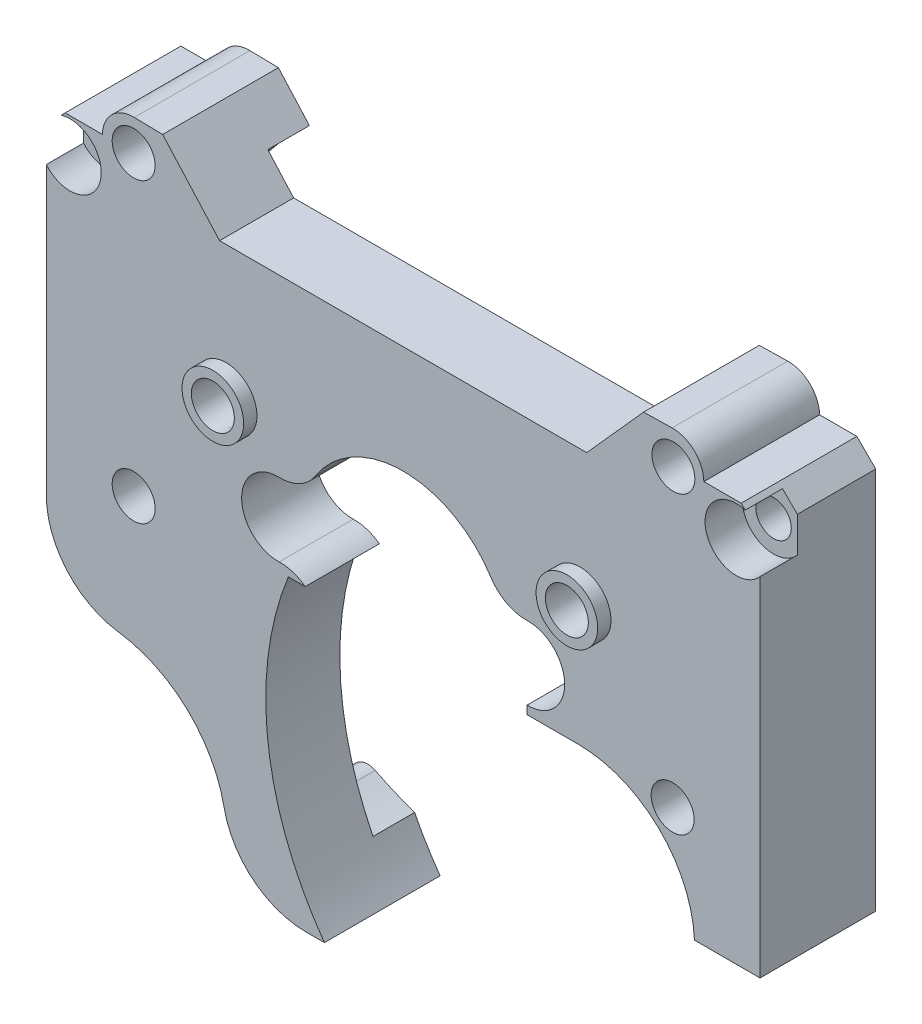
SolidWorks part; units mm, degrees
material "PET"
ref_plane "Front Plane" through (0, 0, 0) normal (0, 0, 1) x (1, 0, 0)
ref_plane "Top Plane" through (0, 0, 0) normal (0, 1, 0) x (1, 0, 0)
ref_plane "Right Plane" through (0, 0, 0) normal (1, 0, 0) x (0, 0, -1)
sketch "Sketch1" plane through (0, 0, 0) normal (0, 0, 1) x (1, 0, 0)
  circle A0 centre (0, 0) radius 24.7015
  circle A1 centre (0, 0) radius 7.9375
  dimension "D1" = 49.403
  dimension "D2" = 15.875
extrude "Boss-Extrude1" add sketch "Sketch1" along normal up to surface (5.65 mm away)
hole_wizard "CBORE SLOT for #2 Pan Head Machine Screw1" positions "Sketch13" profile "Sketch12" size "#2" standard "ANSI Inch" slot yes end condition through all
sketch "Sketch13" plane through (0, 0, 0) normal (0, 0, -1) x (-1, 0, 0)
  line L0 (-2.0066, 13.2132) -> (-2.0066, 19.5632) construction
  line L2 (7.493, 13.2132) -> (7.493, 19.5632) construction
  line L4 (-1.8669, 13.2132) -> (-2.1463, 13.2132) construction
  circle A1 centre (7.493, 14.3181) radius 1.1049 construction
  point P9 (-2.0066, 16.3882)
  point P11 (7.493, 16.3882)
  dimension "D1" = 6.35
sketch "Sketch12" plane through (2.0066, 16.3882, 0) normal (1, 0, 0) x (0, 1, 0)
  line L0 (0, 0) -> (0, 5.65)
  line L1 (0, 5.65) -> (1.3525, 5.65)
  line L3 (1.3525, 5.65) -> (1.3526, 1.5748)
  line L4 (2.3812, 1.5748) -> (1.3526, 1.5748)
  line L5 (2.3812, 1.5748) -> (2.3812, 1.0325)
  line L6 (2.3812, 1.0325) -> (3.4138, 0)
  line L7 (3.4138, 0) -> (0, 0)
  line L8 (-2.3812, 1.0325) -> (-3.4138, 0) construction
  line L11 (0, -6.35) -> (0, 107.95) construction
  dimension "Thru Hole Dia." = 2.7051
  dimension "Thru Hole Depth" = 5.65
  dimension "C'Bore Dia." = 4.7625
  dimension "C'Bore Depth" = 1.5748
  dimension "Near C'Sink Dia." = 6.8275
  dimension "Near C'Sink Angle" = 90
sketch "Sketch11" plane through (0, 0, 5.65) normal (0, 0, 1) x (1, 0, 0)
  line L0 (-24.2881, -4.5) -> (-11.876, -4.5)
  line L1 (-17.5, -4.5) -> (-13.5554, -4.5) construction
  line L2 (0, 0) -> (0, -12.7) construction
  line L3 (24.2881, -4.5) -> (11.876, -4.5)
  arc A0 (-11.876, -4.5) -> (11.876, -4.5) centre (0, 0) ccw
  arc A1 (-24.2881, -4.5) -> (24.2881, -4.5) centre (0, 0) ccw
  circle A2 centre (0, 0) radius 7.9375 construction
  dimension "D1" = 25.4
  dimension "D2" = 49.403
extrude "Boss-Extrude5" add sketch "Sketch11" along normal blind 12.7
sketch "Sketch17" plane through (0, 0, 5.65) normal (0, 0, 1) x (1, 0, 0)
  line L0 (-24.2881, -4.5) -> (-20.4781, -4.5)
  line L1 (-11.876, -4.5) -> (-24.2881, -4.5) construction
  line L2 (-20.4781, -4.5) -> (-20.4781, 4.39)
  line L3 (-13.4931, 20.6906) -> (-13.4931, 4.39) construction
  line L4 (-13.4931, 4.39) -> (-20.4781, 4.39) construction
  line L5 (0, 24.7015) -> (0, 0) construction
  line L6 (13.4931, 4.39) -> (20.4781, 4.39) construction
  line L7 (13.4931, 20.6906) -> (13.4931, 4.39) construction
  line L8 (20.4781, -4.5) -> (20.4781, 4.39)
  line L9 (24.2881, -4.5) -> (20.4781, -4.5)
  line L10 (-13.4931, 16.0175) -> (-13.4931, 20.6906)
  line L11 (13.4931, 16.0175) -> (13.4931, 20.6906)
  arc A0 (-13.4931, 20.6906) -> (-24.2881, -4.5) centre (0, 0) ccw
  arc A1 (24.2881, -4.5) -> (-24.2881, -4.5) centre (0, 0) ccw construction
  arc A2 (13.4931, 20.6906) -> (24.2881, -4.5) centre (0, 0) cw
  arc A3 (-13.4931, 16.0175) -> (-20.4781, 4.39) centre (0, 0) ccw
  arc A4 (20.4781, 4.39) -> (13.4931, 16.0175) centre (0, 0) ccw
  dimension "D1" = 3.81
  dimension "D2" = 6.985
  dimension "D3" = 8.89
extrude "Boss-Extrude7" add sketch "Sketch17" along normal up to surface (12.7 mm away) up to face at (0, -11.6004, 18.35)
sketch "Sketch32" plane through (0, 0, 0) normal (0, 0, -1) x (-1, 0, 0)
  line L0 (-18.3768, 26.4668) -> (18.3768, 26.4668) construction
  line L1 (-27.4725, 17.3712) -> (-18.3768, 26.4668) construction
  line L2 (-27.4725, -17.6276) -> (-27.4725, 17.3712) construction
  line L3 (18.3768, -26.4668) -> (-18.6333, -26.4668) construction
  line L4 (27.4725, -17.3712) -> (18.3768, -26.4668) construction
  line L5 (27.4725, 17.3712) -> (27.4725, -17.3712) construction
  line L6 (18.3768, 26.4668) -> (27.4725, 17.3712) construction
  line L7 (-18.3768, 26.4668) -> (18.3768, 26.4668) construction
  line L8 (-27.4725, 17.3712) -> (-18.3768, 26.4668) construction
  line L9 (-27.4725, -17.6276) -> (-27.4725, 17.3712) construction
  line L10 (18.3768, -26.4668) -> (-18.6333, -26.4668) construction
  line L11 (27.4725, -17.3712) -> (18.3768, -26.4668) construction
  line L12 (27.4725, 17.3712) -> (27.4725, -17.3712) construction
  line L13 (18.3768, 26.4668) -> (27.4725, 17.3712) construction
  line L14 (18.2716, 26.2128) -> (27.2185, 17.266)
  line L15 (27.2185, 17.266) -> (27.2185, -16.7395)
  line L16 (27.2185, -16.7395) -> (29.6895, -16.7395)
  line L17 (16.2895, -26.2128) -> (-18.2716, -26.2128)
  line L18 (-27.2185, -17.266) -> (-27.2185, 17.266)
  line L19 (-27.2185, 17.266) -> (-18.2716, 26.2128)
  line L20 (-18.2716, 26.2128) -> (18.2716, 26.2128)
  line L21 (27.2185, -17.266) -> (18.2716, -26.2128) construction
  line L23 (29.6895, -16.7395) -> (29.6895, -29.2395)
  line L24 (29.6895, -29.2395) -> (16.2895, -29.2395)
  line L25 (16.2895, -29.2395) -> (16.2895, -26.2128)
  line L26 (18.2716, -26.2128) -> (-18.6333, -26.2128) construction
  line L27 (27.2185, 17.266) -> (27.2185, -17.266) construction
  line L28 (-18.2716, -26.2128) -> (-27.2185, -17.266)
  line L29 (-27.2185, -17.6276) -> (-27.2185, 17.266) construction
  arc A0 (-27.4725, -17.6276) -> (-18.6333, -26.4668) centre (-18.6333, -17.6276) ccw construction
  circle A1 centre (0, 0) radius 24.7015
  circle A2 centre (0, 0) radius 24.7015
  arc A3 (-27.4725, -17.6276) -> (-18.6333, -26.4668) centre (-18.6333, -17.6276) ccw construction
  arc A5 (-27.2185, -17.6276) -> (-18.6333, -26.2128) centre (-18.6333, -17.6276) ccw construction
  dimension "D1" = 0
  dimension "D2" = 0.254
extrude "Boss-Extrude8" add sketch "Sketch32" against normal up to surface (18.35 mm away) up to face at (0, 1.1766, 18.35)
sketch "Sketch33" plane through (0, 0, 18.35) normal (0, 0, 1) x (1, 0, 0)
  line L1 (-13.4931, 20.6906) -> (13.4931, 20.6906)
  line L2 (-13.4931, 20.6906) -> (-13.4931, 22.4028)
  line L3 (-13.4931, 26.2128) -> (13.4931, 26.2128)
  line L4 (13.4931, 20.6906) -> (13.4931, 22.4028)
  line L5 (13.4931, 20.6906) -> (13.4931, 16.0175) construction
  line L6 (-18.2716, 26.2128) -> (18.2716, 26.2128) construction
  line L29 (-13.4931, 22.4028) -> (-13.4931, 26.2128)
  line L30 (13.4931, 26.2128) -> (13.4931, 22.4028)
extrude "Cut-Extrude1" cut sketch "Sketch33" against normal up to surface (12.7 mm away) up to face at (-7.9375, 0, 5.65)
sketch "Sketch35" plane through (0, 0, 18.35) normal (0, 0, 1) x (1, 0, 0)
  line L0 (20.4781, 4.39) -> (20.4781, -4.5) construction
  line L1 (13.4931, 26.2128) -> (13.4931, 16.0175) construction
  line L2 (-13.4931, 16.0175) -> (-13.4931, 26.2128) construction
  line L3 (-20.4781, -4.5) -> (-20.4781, 4.39) construction
  line L12 (-20.4781, -4.5) -> (-20.4781, 4.39)
  line L13 (-13.4931, 16.0175) -> (-13.4931, 25.6031)
  line L14 (13.4931, 25.6031) -> (13.4931, 16.0175)
  line L15 (20.4781, 4.39) -> (20.4781, -4.5)
  line L16 (-27.2185, -16.7395) -> (-27.2185, 17.266) construction
  line L17 (-27.2185, 17.266) -> (-18.2716, 26.2128) construction
  line L20 (18.2716, 26.2128) -> (27.2185, 17.266) construction
  line L21 (27.2185, 17.266) -> (27.2185, -17.266) construction
  line L22 (-27.2185, -16.7395) -> (-27.2185, 17.266) construction
  line L23 (-27.2185, 17.266) -> (-18.2716, 26.2128) construction
  line L24 (-23.4085, 15.6878) -> (-15.5775, 23.5187) construction
  line L25 (15.5775, 23.5187) -> (23.4085, 15.6878) construction
  line L26 (18.2716, 26.2128) -> (27.2185, 17.266) construction
  line L27 (27.2185, 17.266) -> (27.2185, -17.266) construction
  line L28 (-23.4085, -4.5) -> (-23.4085, 15.6878)
  line L29 (-23.4085, 15.6878) -> (-13.4931, 25.6031)
  line L30 (13.4931, 25.6031) -> (23.4085, 15.6878)
  line L31 (23.4085, 15.6878) -> (23.4085, -4.5)
  line L32 (-20.4781, -4.5) -> (-23.4085, -4.5)
  line L33 (20.4781, -4.5) -> (23.4085, -4.5)
  line L34 (-23.4085, -16.7395) -> (-23.4085, 15.6878) construction
  line L35 (23.4085, 15.6878) -> (23.4085, -17.266) construction
  arc A0 (20.4781, 4.39) -> (13.4931, 16.0175) centre (0, 0) ccw construction
  arc A1 (-13.4931, 16.0175) -> (-20.4781, 4.39) centre (0, 0) ccw construction
  arc A6 (-13.4931, 16.0175) -> (-20.4781, 4.39) centre (0, 0) ccw
  arc A7 (20.4781, 4.39) -> (13.4931, 16.0175) centre (0, 0) ccw
  dimension "D1" = 3.81
extrude "Cut-Extrude2" cut sketch "Sketch35" against normal up to surface (12.7 mm away) up to face at (-7.9375, 0, 5.65)
sketch "Sketch37" plane through (0, 0, 18.35) normal (0, 0, 1) x (1, 0, 0)
  line L16 (-23.4085, 15.6878) -> (-13.4931, 25.6031)
  line L17 (-13.4931, 25.6031) -> (-13.4931, 26.2128)
  line L18 (-13.4931, 26.2128) -> (-18.2716, 26.2128)
  line L19 (-18.2716, 26.2128) -> (-27.2185, 17.266)
  line L20 (-27.2185, 17.266) -> (-27.2185, -16.7395)
  line L21 (-27.2185, -16.7395) -> (-29.6895, -16.7395)
  line L22 (-16.2895, -26.2128) -> (18.2716, -26.2128)
  line L23 (27.2185, -17.266) -> (27.2185, 17.266)
  line L24 (27.2185, 17.266) -> (18.2716, 26.2128)
  line L25 (18.2716, 26.2128) -> (13.4931, 26.2128)
  line L26 (13.4931, 26.2128) -> (13.4931, 25.6031)
  line L27 (13.4931, 25.6031) -> (23.4085, 15.6878)
  line L28 (23.4085, 15.6878) -> (23.4085, -4.5)
  line L29 (23.4085, -4.5) -> (11.876, -4.5)
  line L30 (-11.876, -4.5) -> (-23.4085, -4.5)
  line L31 (-23.4085, -4.5) -> (-23.4085, 15.6878)
  line L32 (-23.4085, 15.6878) -> (-13.4931, 25.6031)
  line L33 (-13.4931, 25.6031) -> (-13.4931, 26.2128)
  line L34 (-13.4931, 26.2128) -> (-18.2716, 26.2128)
  line L35 (-18.2716, 26.2128) -> (-27.2185, 17.266)
  line L36 (-27.2185, 17.266) -> (-27.2185, -16.7395)
  line L37 (-27.2185, -16.7395) -> (-29.6895, -16.7395)
  line L38 (-16.2895, -26.2128) -> (18.2716, -26.2128)
  line L39 (27.2185, -17.266) -> (27.2185, 17.266)
  line L40 (27.2185, 17.266) -> (18.2716, 26.2128)
  line L41 (18.2716, 26.2128) -> (13.4931, 26.2128)
  line L42 (13.4931, 26.2128) -> (13.4931, 25.6031)
  line L43 (13.4931, 25.6031) -> (23.4085, 15.6878)
  line L44 (23.4085, 15.6878) -> (23.4085, -4.5)
  line L45 (23.4085, -4.5) -> (11.876, -4.5)
  line L46 (-11.876, -4.5) -> (-23.4085, -4.5)
  line L47 (-23.4085, -4.5) -> (-23.4085, 15.6878)
  line L52 (-29.6895, -16.7395) -> (-29.6895, -29.2395)
  line L53 (-29.6895, -16.7395) -> (-29.6895, -29.2395)
  line L54 (-29.6895, -29.2395) -> (-16.2895, -29.2395)
  line L55 (-29.6895, -29.2395) -> (-16.2895, -29.2395)
  line L56 (-16.2895, -29.2395) -> (-16.2895, -26.2128)
  line L57 (-16.2895, -29.2395) -> (-16.2895, -26.2128)
  line L58 (18.2716, -26.2128) -> (27.2185, -17.266)
  line L59 (18.2716, -26.2128) -> (27.2185, -17.266)
  arc A3 (-11.876, -4.5) -> (11.876, -4.5) centre (0, 0) ccw
  arc A5 (-11.876, -4.5) -> (11.876, -4.5) centre (0, 0) ccw
  dimension "D1" = 0
extrude "Cut-Extrude3" cut sketch "Sketch37" against normal up to surface (12.7 mm away) up to face at (-3.5089, 1.6246, 18.35)
hole_wizard "Hole1" positions "Sketch41" profile "Sketch40" legacy
sketch "Sketch41" plane through (0, 0, 5.65) normal (0, 0, 1) x (1, 0, 0)
  line L0 (-13.8885, -4) -> (-27.2185, -4) construction
  line L1 (-27.2185, 17.266) -> (-27.2185, -16.7395) construction
  line L3 (-20.5535, -4) -> (-20.5535, 26.2128) construction
  line L5 (18.2716, 26.2128) -> (-18.2716, 26.2128) construction
  line L6 (-20.5535, 26.2128) -> (-20.5535, 11.1064)
  line L10 (13.8885, -4) -> (27.2185, -4) construction
  line L11 (27.2185, -17.266) -> (27.2185, 17.266) construction
  point P0 (-20.5535, 18.6596)
  point P3 (-20.5535, -4)
  point P6 (20.6092, 18.5346)
  point P57 (20.5535, -4)
  point P58 (-20.5535, -4)
  point P60 (20.5535, -4)
  point P62 (-20.5535, 18.5346)
sketch "Sketch40" plane through (-20.5535, 18.6596, 5.65) normal (1, 0, 0) x (0, -1, 0)
  line L0 (0, 0) -> (0, 2.921)
  line L1 (0, 2.921) -> (1.4986, 2.921)
  line L2 (1.4986, 2.921) -> (1.6383, 0)
  line L3 (1.6383, 0) -> (0, 0)
  line L4 (0, 110) -> (0, -10) construction
  dimension "Minor Diameter" = 2.9972
  dimension "Depth" = 2.921
  dimension "Major Diameter" = 3.2766
hole_wizard "Ø3.0 (3) Diameter Hole1" positions "Sketch43" profile "Sketch42" hole size "Ø3.0" standard "ANSI Metric" end condition through all
sketch "Sketch43" plane through (0, 0, 5.65) normal (0, 0, 1) x (1, 0, 0)
  circle A0 centre (20.5535, -4) radius 1.4986 construction
  point P0 (-20.5535, 18.6596)
  point P3 (20.6092, 18.5346)
  point P6 (-20.5535, -4)
  point P13 (20.5535, -4)
  point P16 (0, 0)
  point P17 (0, 0)
  point P18 (0, 0)
sketch "Sketch42" plane through (-20.5535, 18.6596, 5.65) normal (1, 0, 0) x (0, -1, 0)
  line L0 (0, 0) -> (0, 5.65)
  line L1 (0, 5.65) -> (1.5, 5.65)
  line L2 (1.5, 5.65) -> (1.5, 0)
  line L5 (1.5, 0) -> (0, 0)
  line L11 (0, -6.35) -> (0, 107.95) construction
  dimension "Thru Hole Dia." = 3
  dimension "Thru Hole Depth" = 5.65
sketch "Sketch44" plane through (0, 0, 5.65) normal (0, 0, 1) x (1, 0, 0)
  line L0 (0, 0) -> (0, -7.9375) construction
  circle A0 centre (-9.525, 0) radius 2.794
  circle A1 centre (0, 0) radius 7.9375 construction
  circle A2 centre (9.525, 0) radius 2.794
  dimension "D1" = 5.588
extrude "Cut-Extrude4" cut sketch "Sketch44" against normal through all
fillet "Fillet1" radius 1.27 2 edges at (-16.2895, -26.2128, 2.825) (-27.2185, -16.7395, 2.825)
sketch "Sketch45" plane through (0, 0, 0) normal (0, 0, -1) x (-1, 0, 0)
  line L0 (22.9895, -29.2395) -> (22.9895, -22.9895) construction
  line L1 (16.2895, -29.2395) -> (29.6895, -29.2395) construction
  line L2 (22.9895, -22.9895) -> (29.6895, -22.9895) construction
  line L3 (29.6895, -29.2395) -> (29.6895, -16.7395) construction
  line L5 (19.5254, -16.9895) -> (16.0613, -22.9895)
  line L6 (16.0613, -22.9895) -> (19.5254, -28.9895)
  line L7 (19.5254, -28.9895) -> (26.4536, -28.9895)
  line L8 (26.4536, -28.9895) -> (29.9177, -22.9895)
  line L9 (29.9177, -22.9895) -> (26.4536, -16.9895)
  line L10 (26.4536, -16.9895) -> (19.5254, -16.9895)
  circle A0 centre (22.9895, -22.9895) radius 6 construction
  dimension "D1" = 12
extrude "Cut-Extrude5" cut sketch "Sketch45" against normal through all
sketch "Sketch46" plane through (0, 0, 0) normal (0, 0, -1) x (-1, 0, 0)
  line L14 (19.5254, -16.9895) -> (26.4536, -16.9895)
  line L15 (19.5254, -16.9895) -> (26.4536, -16.9895)
  line L16 (29.6895, -22.5942) -> (29.6895, -16.7395)
  line L17 (27.2185, -15.4695) -> (27.2185, 17.266)
  line L18 (27.2185, 17.266) -> (18.2716, 26.2128)
  line L19 (18.2716, 26.2128) -> (-18.2716, 26.2128)
  line L20 (-18.2716, 26.2128) -> (-27.2185, 17.266)
  line L21 (-27.2185, 17.266) -> (-27.2185, -17.266)
  line L22 (-27.2185, -17.266) -> (-18.2716, -26.2128)
  line L23 (-18.2716, -26.2128) -> (15.0195, -26.2128)
  line L24 (16.2895, -27.4828) -> (16.2895, -29.2395)
  line L25 (16.2895, -29.2395) -> (29.6895, -29.2395)
  line L26 (26.4536, -16.9895) -> (29.6895, -22.5942)
  line L27 (26.4536, -16.9895) -> (29.6895, -22.5942)
  line L28 (19.5254, -28.9895) -> (16.0613, -22.9895)
  line L29 (19.5254, -28.9895) -> (16.0613, -22.9895)
  line L30 (29.6895, -22.5942) -> (29.6895, -16.7395)
  line L31 (27.2185, -15.4695) -> (27.2185, 17.266)
  line L32 (27.2185, 17.266) -> (18.2716, 26.2128)
  line L33 (18.2716, 26.2128) -> (-18.2716, 26.2128)
  line L34 (-18.2716, 26.2128) -> (-27.2185, 17.266)
  line L35 (-27.2185, 17.266) -> (-27.2185, -17.266)
  line L36 (-27.2185, -17.266) -> (-18.2716, -26.2128)
  line L37 (-18.2716, -26.2128) -> (15.0195, -26.2128)
  line L38 (16.2895, -27.4828) -> (16.2895, -29.2395)
  line L39 (16.2895, -29.2395) -> (29.6895, -29.2395)
  line L40 (16.0613, -22.9895) -> (19.5254, -16.9895)
  line L41 (16.0613, -22.9895) -> (19.5254, -16.9895)
  line L46 (29.6895, -16.7395) -> (28.4885, -16.7395)
  line L47 (29.6895, -16.7395) -> (28.4885, -16.7395)
  line L48 (29.6895, -29.2395) -> (29.6895, -23.3847)
  line L49 (29.6895, -29.2395) -> (29.6895, -23.3847)
  line L50 (29.6895, -23.3847) -> (26.4536, -28.9895)
  line L51 (29.6895, -23.3847) -> (26.4536, -28.9895)
  line L52 (26.4536, -28.9895) -> (19.5254, -28.9895)
  line L53 (26.4536, -28.9895) -> (19.5254, -28.9895)
  circle A0 centre (0, 0) radius 23.8252 construction
  circle A1 centre (0, 0) radius 24.3332
  arc A7 (27.2185, -15.4695) -> (28.4885, -16.7395) centre (28.4885, -15.4695) ccw
  arc A8 (16.2895, -27.4828) -> (15.0195, -26.2128) centre (15.0195, -27.4828) ccw
  arc A11 (27.2185, -15.4695) -> (28.4885, -16.7395) centre (28.4885, -15.4695) ccw
  arc A12 (16.2895, -27.4828) -> (15.0195, -26.2128) centre (15.0195, -27.4828) ccw
  dimension "D1" = 47.6504
  dimension "D2" = 0.508
  dimension "D3" = 0
extrude "Boss-Extrude9" add sketch "Sketch46" along normal blind 3.175
fillet "Fillet3" radius 3.175 4 edges at (7.66, 2.0804, 2.825) (7.66, -2.0804, 2.825) (-7.66, -2.0804, 2.825) (-7.66, 2.0804, 2.825)
sketch "Sketch47" plane through (0, 0, 5.65) normal (0, 0, 1) x (1, 0, 0)
  line L0 (-29.6895, -22.5942) -> (-29.6895, -28.9895)
  line L1 (-29.6895, -28.9895) -> (-19.5254, -28.9895)
  line L2 (-29.6895, -22.5942) -> (-26.4536, -16.9895) construction
  line L3 (-26.4536, -16.9895) -> (-19.5254, -16.9895) construction
  line L4 (-19.5254, -16.9895) -> (-16.0613, -22.9895) construction
  line L5 (-16.0613, -22.9895) -> (-19.5254, -28.9895) construction
  line L6 (-29.6895, -22.5942) -> (-26.4536, -16.9895)
  line L7 (-26.4536, -16.9895) -> (-19.5254, -16.9895)
  line L8 (-19.5254, -16.9895) -> (-16.0613, -22.9895)
  line L9 (-16.0613, -22.9895) -> (-19.5254, -28.9895)
extrude "Boss-Extrude10" add sketch "Sketch47" against normal through all
fillet "Fillet2" radius 1.27 3 edges at (-29.6895, -16.7395, 1.2375) (-16.2895, -29.2395, 1.2375) (-29.6895, -29.2395, 1.2375)
sketch "Sketch48" plane through (0, 0, -3.175) normal (0, 0, -1) x (-1, 0, 0)
  circle A0 centre (22.9895, -22.9895) radius 9.525
  dimension "D1" = 19.05
extrude "Cut-Extrude6" cut sketch "Sketch48" against normal through all
fillet "Fillet4" radius 6.35 2 edges at (-14.0264, -26.2128, 1.2375) (-27.2185, -14.4548, 1.2375)
fillet "Fillet5" radius 1.27 2 edges at (-13.9718, -19.9222, -1.5875) (-19.9222, -13.9718, -1.5875)
hole_wizard "CBORE for #2 Pan Head Machine Screw1" positions "Sketch50" profile "Sketch49" counterbore size "#2" standard "ANSI Inch" end condition through all
sketch "Sketch50" plane through (0, 0, 5.65) normal (0, 0, 1) x (1, 0, 0)
  point P0 (-25.4059, 16.1162)
  point P3 (25.4059, 16.1162)
  point P6 (17.2045, -24.6819)
sketch "Sketch49" plane through (-25.4059, 16.1162, 5.65) normal (1, 0, 0) x (0, -1, 0)
  line L0 (0, 0) -> (0, 8.825)
  line L1 (0, 8.825) -> (1.3525, 8.825)
  line L3 (1.3525, 8.825) -> (1.3525, 2.8448)
  line L4 (1.3525, 2.8448) -> (2.3812, 2.8448)
  line L5 (2.3812, 2.8448) -> (2.3812, 0)
  line L7 (2.3812, 0) -> (0, 0)
  line L11 (0, -6.35) -> (0, 107.95) construction
  dimension "Thru Hole Dia." = 2.7051
  dimension "Thru Hole Depth" = 8.825
  dimension "C'Bore Dia." = 4.7625
  dimension "C'Bore Depth" = 2.8448
sketch "Sketch51" plane through (0, 0, -3.175) normal (0, 0, 1) x (1, 0, 0)
  line L0 (-8.7558, -3.429) -> (13.335, -3.429)
  line L1 (7.0488, -18.6052) -> (-3.503, -29.157)
  line L2 (13.335, -12.319) -> (7.0488, -18.6052) construction
  arc A0 (-8.7558, -3.429) -> (-3.503, -29.157) centre (13.335, -12.319) ccw
  arc A1 (7.0488, -18.6052) -> (13.335, -3.429) centre (13.335, -12.319) ccw
  point P1 (0, 0)
  dimension "D1" = 47.625
  dimension "D2" = 17.78
  dimension "D3" = 45
extrude "Cut-Extrude7" cut sketch "Sketch51" along normal up to next
sketch "Sketch52" plane through (0, 0, 5.65) normal (0, 0, 1) x (1, 0, 0)
  line L0 (27.2185, -17.266) -> (27.2185, 14.5718) construction
  line L1 (9.4546, -2.7931) -> (5.9351, -2.7931)
  line L2 (9.4546, -2.7931) -> (9.4546, -5.2705)
  line L3 (9.4546, -5.2705) -> (5.9351, -5.2705)
  line L4 (5.9351, -2.7931) -> (5.9351, -5.2705)
  line L5 (-5.9351, -5.2705) -> (-6.6961, -5.2705)
  line L6 (-5.9351, -5.2705) -> (-5.9351, -4.2622)
  line L7 (-5.9351, -4.2622) -> (-6.6961, -4.2622)
  line L8 (-6.6961, -5.2705) -> (-6.6961, -4.2622)
  line L9 (27.2185, -11.9378) -> (-0.5588, -11.9378)
  line L10 (27.2185, -11.9378) -> (27.2185, -26.2128)
  line L11 (27.2185, -26.2128) -> (-0.5588, -26.2128)
  line L12 (-0.5588, -11.9378) -> (-0.5588, -26.2128)
  line L13 (7.0488, -18.6052) -> (7.0488, -5.2705) construction
  point P22 (7.0488, -11.9378)
extrude "Cut-Extrude8" cut sketch "Sketch52" against normal through all body kept at (18.2716, 26.2128, 5.65)
sketch "Sketch53" plane through (0, 0, 5.65) normal (0, 0, 1) x (1, 0, 0)
  circle A4 centre (13.5, 6) radius 2.35 construction
  circle A5 centre (13.5, 6) radius 2.35
  circle A6 centre (-13.5, 6) radius 2.35 construction
  circle A7 centre (-13.5, 6) radius 2.35
extrude "Boss-Extrude11" add sketch "Sketch53" along normal up to surface (1.013 mm away)
fillet "Fillet6" [suppressed] radius 2.54
sketch "Sketch54" plane through (0, 0, 0) normal (0, 0, -1) x (-1, 0, 0)
  line L2 (1.4072, 14.5658) -> (1.4072, 18.2107)
  line L3 (-5.4204, 18.2107) -> (-5.4204, 14.5658)
  line L4 (1.4072, 14.5658) -> (1.4072, 18.2107)
  line L5 (-5.4204, 18.2107) -> (-5.4204, 14.5658)
  line L6 (4.0792, 18.2107) -> (4.0792, 14.5658)
  line L7 (10.9068, 14.5658) -> (10.9068, 18.2107)
  line L8 (4.0792, 18.2107) -> (4.0792, 14.5658)
  line L9 (10.9068, 14.5658) -> (10.9068, 18.2107)
  arc A3 (1.4072, 18.2107) -> (-5.4204, 18.2107) centre (-2.0066, 18.2107) ccw
  arc A4 (-5.4204, 14.5658) -> (1.4072, 14.5658) centre (-2.0066, 14.5658) ccw
  arc A5 (1.4072, 18.2107) -> (-5.4204, 18.2107) centre (-2.0066, 18.2107) ccw
  arc A6 (-5.4204, 14.5658) -> (1.4072, 14.5658) centre (-2.0066, 14.5658) ccw
  arc A7 (10.9068, 18.2107) -> (4.0792, 18.2107) centre (7.493, 18.2107) ccw
  arc A8 (4.0792, 14.5658) -> (10.9068, 14.5658) centre (7.493, 14.5658) ccw
  arc A9 (10.9068, 18.2107) -> (4.0792, 18.2107) centre (7.493, 18.2107) ccw
  arc A10 (4.0792, 14.5658) -> (10.9068, 14.5658) centre (7.493, 14.5658) ccw
  dimension "D1" = 0
  dimension "D2" = 0
extrude "Boss-Extrude12" add sketch "Sketch54" against normal up to surface (5.65 mm away) up to face at (-15.85, 6, 5.65)
hole_wizard "#0 Clearance Hole1" positions "Sketch55" profile "Sketch56" hole size "#0" standard "ANSI Inch" end condition up to next
sketch "Sketch55" plane through (0, 0, 0) normal (0, 0, -1) x (-1, 0, 0)
  point P0 (-13.5, 6)
  point P3 (13.5, 6)
sketch "Sketch56" plane through (13.5, 6, 0) normal (1, 0, 0) x (0, 1, 0)
  line L0 (0, 0) -> (0, 6.663)
  line L1 (0, 6.663) -> (0.9271, 6.663)
  line L2 (0.9271, 6.663) -> (0.9271, 0)
  line L5 (0.9271, 0) -> (0, 0)
  line L11 (0, -6.35) -> (0, 107.95) construction
  dimension "Thru Hole Dia." = 1.8542
  dimension "Thru Hole Depth" = 6.663
hole_wizard "Hole2" positions "Sketch57" profile "Sketch58" legacy
sketch "Sketch57" plane through (0, 0, 6.663) normal (0, 0, 1) x (1, 0, 0)
  point P0 (-13.5, 6)
  point P3 (13.5, 6)
sketch "Sketch58" plane through (-13.5, 6, 6.663) normal (1, 0, 0) x (0, -1, 0)
  line L0 (0, 0) -> (0, 2.921)
  line L1 (0, 2.921) -> (1.4986, 2.921)
  line L2 (1.4986, 2.921) -> (1.6383, 0)
  line L3 (1.6383, 0) -> (0, 0)
  line L4 (0, 110) -> (0, -10) construction
  dimension "Minor Diameter" = 2.9972
  dimension "Depth" = 2.921
  dimension "Major Diameter" = 3.2766
sketch "Sketch59" plane through (0, 0, 5.65) normal (0, 0, 1) x (1, 0, 0)
  circle A0 centre (20.6092, 18.5346) radius 1.5 construction
  circle A1 centre (-20.5535, 18.6596) radius 1.5 construction
  circle A2 centre (20.6092, 18.5346) radius 1.5
  circle A3 centre (-20.5535, 18.6596) radius 1.5
extrude "Cut-Extrude9" cut sketch "Sketch59" against normal through all
sketch "Sketch60" plane through (0, 0, 5.65) normal (0, 0, 1) x (1, 0, 0)
  line L0 (18.2716, 26.2128) -> (-18.2716, 26.2128) construction
  line L1 (-18.2716, 26.2128) -> (-26.0862, 18.3982) construction
  line L2 (-25.7794, 18.705) -> (-22.9343, 18.705) construction
  line L3 (-20.5081, 21.0404) -> (-18.3398, 20.9991) construction
  line L4 (-18.3398, 20.9991) -> (-14, 16.1533) construction
  line L5 (18.2716, 26.2128) -> (-18.2716, 26.2128)
  line L6 (-18.2716, 26.2128) -> (-25.7794, 18.705)
  line L7 (-25.7794, 18.705) -> (-22.9343, 18.705)
  line L8 (-20.5081, 21.0404) -> (-18.3398, 20.9991)
  line L9 (-18.3398, 20.9991) -> (-14, 16.1533)
  line L10 (14, 16.1533) -> (18.3398, 20.9991) construction
  line L11 (18.3398, 20.9991) -> (20.5081, 21.0404) construction
  line L12 (22.9343, 18.705) -> (25.7794, 18.705) construction
  line L13 (26.0862, 18.3982) -> (18.2716, 26.2128) construction
  line L14 (14, 16.1533) -> (18.3398, 20.9991)
  line L15 (18.3398, 20.9991) -> (20.5081, 21.0404)
  line L16 (22.9343, 18.705) -> (25.7794, 18.705)
  line L17 (25.7794, 18.705) -> (18.2716, 26.2128)
  line L18 (-14, 16.1533) -> (14, 16.1533)
  arc A0 (-20.5081, 21.0404) -> (-22.9343, 18.705) centre (-20.5535, 18.6596) ccw construction
  arc A1 (-20.5081, 21.0404) -> (-22.9343, 18.705) centre (-20.5535, 18.6596) ccw
  arc A2 (22.9343, 18.705) -> (20.5081, 21.0404) centre (20.5535, 18.6596) ccw construction
  arc A3 (22.9343, 18.705) -> (20.5081, 21.0404) centre (20.5535, 18.6596) ccw
  point P9 (25.6012, 18.8832)
  point P16 (-25.5908, 18.8936)
extrude "Cut-Extrude10" cut sketch "Sketch60" against normal through all
